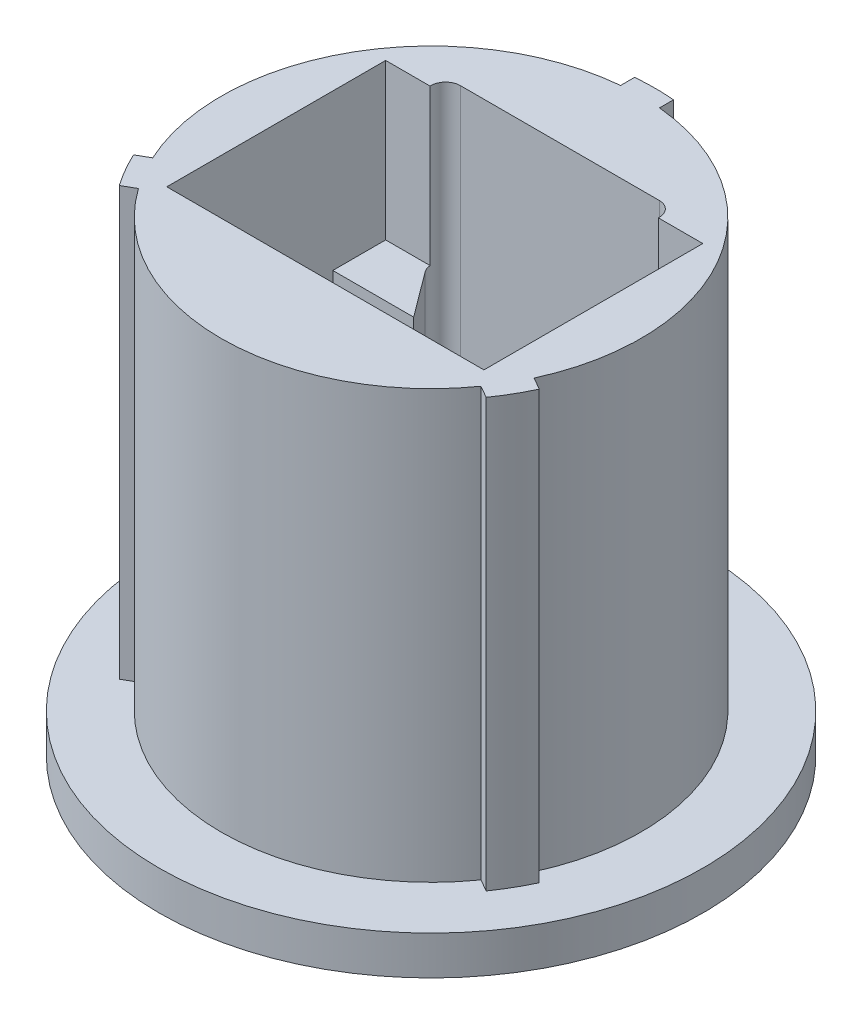
SolidWorks part; units mm, degrees
ref_plane "Front Plane" through (0, 0, 0) normal (0, 0, 1) x (1, 0, 0)
ref_plane "Top Plane" through (0, 0, 0) normal (0, 1, 0) x (1, 0, 0)
ref_plane "Right Plane" through (0, 0, 0) normal (1, 0, 0) x (0, 0, -1)
sketch "Sketch1" plane through (0, 0, 0) normal (0, 1, 0) x (1, 0, 0)
  line L0 (-0.7938, 9.1095) -> (-0.7938, 8.5357)
  line L1 (0.7937, 9.1095) -> (0.7937, 8.5357)
  line L2 (8.2859, -3.8673) -> (7.789, -3.5804)
  line L3 (7.4922, -5.2421) -> (6.9952, -4.9552)
  line L4 (-7.4922, -5.2421) -> (-6.9952, -4.9552)
  line L5 (-8.2859, -3.8673) -> (-7.789, -3.5804)
  arc A0 (-6.9952, -4.9552) -> (6.9952, -4.9552) centre (0, 0) ccw
  arc A1 (-8.2859, -3.8673) -> (-7.4922, -5.2421) centre (0, 0) ccw
  arc A2 (0.7937, 9.1095) -> (-0.7938, 9.1095) centre (0, 0) ccw
  arc A3 (7.4922, -5.2421) -> (8.2859, -3.8673) centre (0, 0) ccw
  arc A4 (7.789, -3.5804) -> (0.7937, 8.5357) centre (0, 0) ccw
  arc A5 (-0.7938, 8.5357) -> (-7.789, -3.5804) centre (0, 0) ccw
  point P18 (0, 0)
  dimension "D1" = 17.145
  dimension "D2" = 18.288
  dimension "D3" = 1.5875
  dimension "D4" = 3
extrude "Boss-Extrude1" add sketch "Sketch1" along normal blind 19.05
sketch "Sketch2" plane through (0, 19.05, 0) normal (0, 1, 0) x (1, 0, 0)
  line L0 (-3.175, 2.4638) -> (-4.5436, 4.3031)
  line L1 (-6.477, 2.4638) -> (6.477, 2.4638)
  line L2 (-6.477, 2.4638) -> (-6.477, 0.762)
  line L3 (-6.477, 0.762) -> (6.477, 0.762)
  line L4 (6.477, 2.4638) -> (6.477, 0.762)
  line L5 (-4.064, 5.2578) -> (4.064, 5.2578)
  line L6 (4.5436, 4.3031) -> (3.175, 2.4638)
  line L7 (3.175, 2.4638) -> (-3.175, 2.4638)
  arc A0 (-4.5436, 4.3031) -> (-4.064, 5.2578) centre (-4.064, 4.66) cw
  arc A1 (4.064, 5.2578) -> (4.5436, 4.3031) centre (4.064, 4.66) cw
  point P12 (0, 5.2578)
  point P13 (0, 2.4638)
  dimension "D1" = 1.7018
  dimension "D2" = 12.954
  dimension "D3" = 8.128
  dimension "D4" = 6.35
  dimension "D5" = 2.794
  dimension "D6" = 0.762
extrude "Cut-Extrude1" cut sketch "Sketch2" against normal through all contours A1 L5 A0 L0 L1 L6 region at (0, 19.05, -3.9469)
extrude "Cut-Extrude2" cut sketch "Sketch2<4>" against normal blind 18.2562 contours L4 L1 L2 L3 region at (0, 19.05, -1.6129)
sketch "Sketch2<4>" plane through (0, 19.05, 0) normal (0, 1, 0) x (1, 0, 0) same geometry as "Sketch2"
sketch "Sketch6" plane through (0, 0, 0) normal (1, 0, 0) x (0, 0, -1)
  line L0 (8.5357, 1.5875) -> (9.144, 1.5875)
  line L1 (8.5357, 1.5875) -> (8.5357, 0)
  line L3 (8.5357, 0) -> (9.144, 0)
  line L5 (9.144, 0) -> (9.144, 1.5875)
  line L6 (0, 19.7302) -> (0, -0.9338) construction
  dimension "D1" = 1.5875
revolve "Cut-Revolve2" cut sketch "Sketch6" angle 360 about L6
sketch "Sketch8" plane through (0, 0, 0) normal (1, 0, 0) x (0, 0, -1)
  line L1 (8.5357, 1.5875) -> (11.1125, 1.5875)
  line L2 (8.5357, 1.5875) -> (8.5357, 0)
  line L3 (8.5357, 0) -> (11.1125, 0)
  line L4 (11.1125, 1.5875) -> (11.1125, 0)
  line L8 (0, 4.4839) -> (0, -1.895) construction
  dimension "D1" = 11.1125
revolve "Revolve2" add sketch "Sketch8" angle 360 about L8
sketch "Sketch9" plane through (0, 19.05, 0) normal (0, 1, 0) x (1, 0, 0)
  line L1 (-6.477, 0.762) -> (6.477, 0.762)
  line L2 (-6.477, 0.762) -> (-6.477, -4.318)
  line L3 (-6.477, -4.318) -> (6.477, -4.318)
  line L4 (6.477, 0.762) -> (6.477, -4.318)
  line L5 (-6.477, 2.4638) -> (6.477, 2.4638)
  line L6 (-6.477, 2.4638) -> (-6.477, 4.6228)
  line L7 (-6.477, 4.6228) -> (6.477, 4.6228)
  line L8 (6.477, 2.4638) -> (6.477, 4.6228)
  dimension "D1" = 5.08
  dimension "D2" = 2.159
extrude "Cut-Extrude3" cut sketch "Sketch9" against normal blind 6.35
sketch "Sketch10" plane through (0, 0, -0.762) normal (0, 0, -1) x (-1, 0, 0)
  line L0 (-6.477, 0.7938) -> (-6.477, 12.7) construction
  line L1 (6.477, 0.7938) -> (-6.477, 0.7938) construction
  line L2 (6.477, 0.7938) -> (6.477, 12.7) construction
  circle A0 centre (-4.572, 7.3978) radius 1.016
  circle A1 centre (4.445, 7.3978) radius 1.016
  point P4 (-6.477, 6.7469)
  dimension "D1" = 1.905
  dimension "D3" = 2.032
  dimension "D2" = 6.604
  dimension "D4" = 2.032
